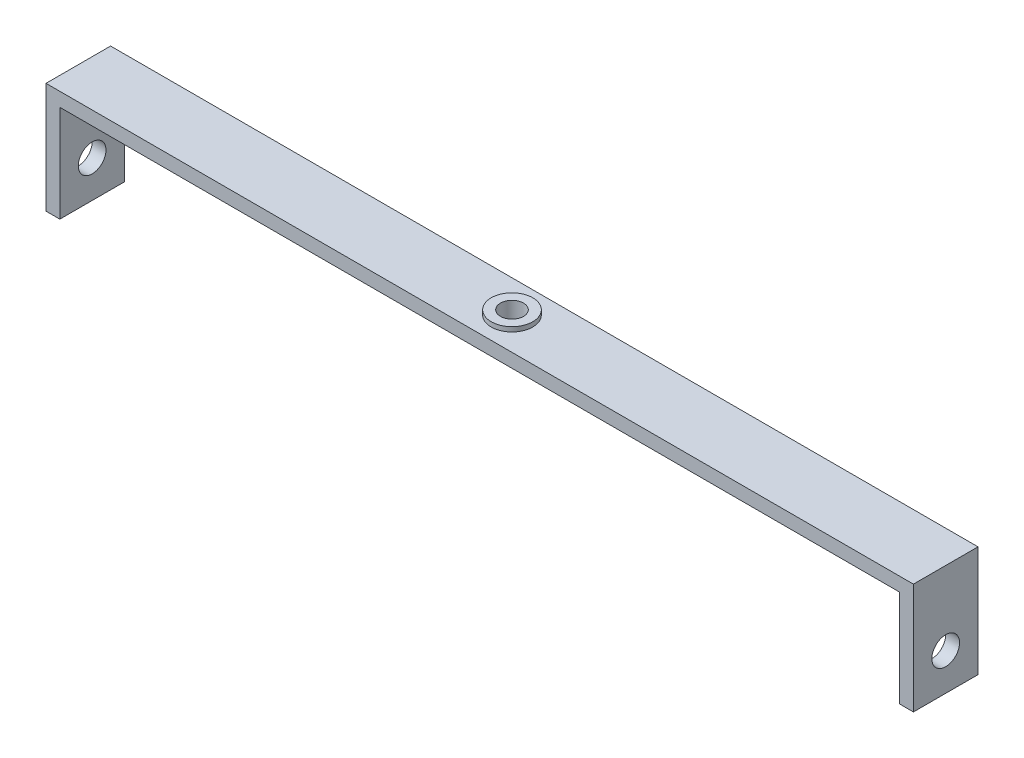
SolidWorks part; units mm, degrees
ref_plane "Front Plane" through (0, 0, 0) normal (0, 0, 1) x (1, 0, 0)
ref_plane "Top Plane" through (0, 0, 0) normal (0, 1, 0) x (1, 0, 0)
ref_plane "Right Plane" through (0, 0, 0) normal (1, 0, 0) x (0, 0, -1)
sketch "Sketch1" plane through (0, 0, 0) normal (0, 0, 1) x (1, 0, 0)
  line L0 (-47, 0) -> (47, 0)
  line L1 (-47, -12) -> (-47, 0)
  line L2 (47, 0) -> (47, -12)
  line L3 (47, -12) -> (46.5841, -12)
  line L4 (-47, -12) -> (-45.5, -12)
  line L5 (-45.5, -12) -> (-45.5, -1.5)
  line L6 (-45.5, -1.5) -> (45.5, -1.5)
  line L7 (45.5, -1.5) -> (45.5, -12)
  line L8 (45.5, -12) -> (46.5841, -12)
  point P10 (0, 0)
  dimension "D1" = 94
  dimension "D2" = 12
  dimension "D3" = 12
  dimension "D4" = 1.5
extrude "Boss-Extrude3" add sketch "Sketch1" along normal blind 3.5 and the other way blind 3.5
sketch "Sketch4" plane through (0, 0, 0) normal (0, 1, 0) x (1, 0, 0)
  circle A0 centre (0, 0) radius 1.25
  dimension "D1" = 2.5
extrude "Cut-Extrude1" cut sketch "Sketch4" against normal blind 3.5
sketch "Sketch5" plane through (0, 0, 0) normal (0, 1, 0) x (1, 0, 0)
  circle A0 centre (0, 0) radius 1.25 construction
  circle A1 centre (0, 0) radius 1.25
  circle A2 centre (0, 0) radius 2.25
  dimension "D1" = 1
extrude "Boss-Extrude5" add sketch "Sketch5" along normal blind 0.5
sketch "Sketch8" plane through (0, 0, 0) normal (1, 0, 0) x (0, 0, -1)
  line L0 (0, 0.5) -> (0, -8) construction
  line L1 (2.25, 0.5) -> (-2.25, 0.5) construction
  circle A0 centre (0, -8) radius 1.5
  dimension "D2" = 3
  dimension "D1" = 8.5
extrude "Cut-Extrude3" cut sketch "Sketch8" along normal up to surface (47 mm away) up to face at (47, -6, 0)
sketch "Sketch10" plane through (0, 0, 0) normal (1, 0, 0) x (0, 0, -1)
  line L0 (0, 0.5) -> (0, -8) construction
  line L1 (1.25, 0.5) -> (-1.25, 0.5) construction
  circle A0 centre (0, -8) radius 1.5
  dimension "D2" = 3
  dimension "D1" = 8.5
extrude "Cut-Extrude4" cut sketch "Sketch10" against normal up to surface (47 mm away) up to face at (-47, -6, 0)
